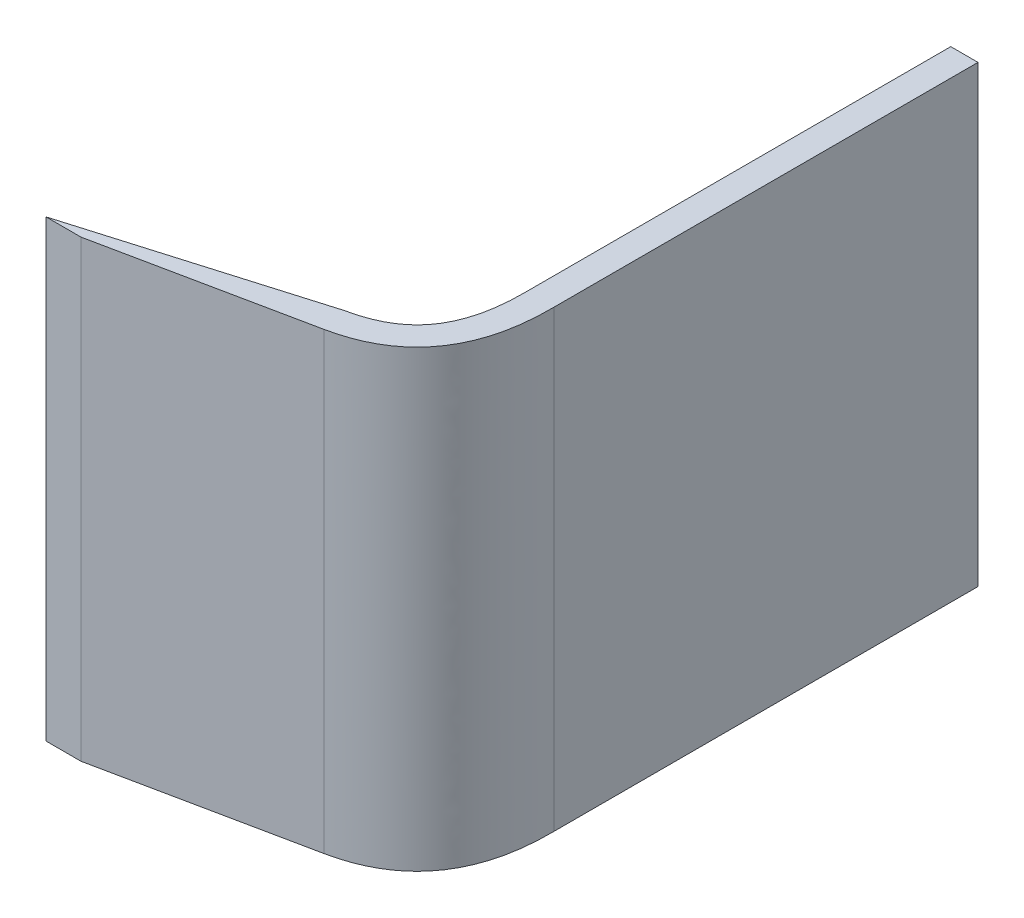
SolidWorks part; units mm, degrees
material "Perspex (TM) GS Acrylic Cast Sheet"
ref_plane "Front Plane" through (0, 0, 0) normal (0, 0, 1) x (1, 0, 0)
ref_plane "Top Plane" through (0, 0, 0) normal (0, 1, 0) x (1, 0, 0)
ref_plane "Right Plane" through (0, 0, 0) normal (1, 0, 0) x (0, 0, -1)
sketch "Sketch1" plane through (0, 0, 0) normal (0, 1, 0) x (1, 0, 0)
  line L0 (0, 46.72) -> (0, 0)
  line L2 (3, 0) -> (3, 46.72)
  line L3 (3, 46.72) -> (0, 46.72)
  line L4 (-8.1614, -11.8261) -> (-33.5868, -19.3412)
  line L5 (-29.7248, -19.3412) -> (-7.554, -14.764)
  line L6 (-33.5868, -19.3412) -> (-29.7248, -19.3412)
  line L7 (0.0002, -0.0334) -> (3, 0)
  line L8 (0, 0) -> (0.0002, -0.0334)
  spline S0 degree 1 poles (0.0002, -0.0334) (-8.1614, -11.8261) knots 0 0 1 1 construction
  spline S1 degree 2 poles (3, 0) (3.1399, -12.5531) (-7.554, -14.764) knots 0 0 0 1 1 1
  spline S2 degree 3 poles (0.0002, -0.0334) (0.0052, -0.4868) (-0.0095, -1.4173) (-0.1374, -3.0879) (-0.4716, -4.9478) (-1.1168, -6.7822) (-1.9737, -8.2695) (-3.0429, -9.4773) (-4.3717, -10.472) (-5.7648, -11.143) (-7.0595, -11.5706) (-7.7988, -11.7512) (-8.1614, -11.8261) knots 0 0 0 0 0.0625 0.125 0.25 0.375 0.5 0.625 0.75 0.875 0.9375 1 1 1 1
  dimension "D2" = 3
  dimension "D4" = 0.0002
  dimension "D5" = 1.6895
  dimension "D6" = 7.554
  dimension "D7" = 8.1614
  dimension "D8" = 29.7248
  dimension "D9" = 33.5868
  dimension "D10" = 19.3412
  dimension "D11" = 46.72
  dimension "D3" = 3
extrude "Boss-Extrude1" add sketch "Sketch1" along normal blind 50 contours L0 L8 L7 L2 L3 | L7 S2 L4 L6 L5 S1 region at (1.4998, 0, -23.3516) region at (1.5047, 0, 0.4306)
